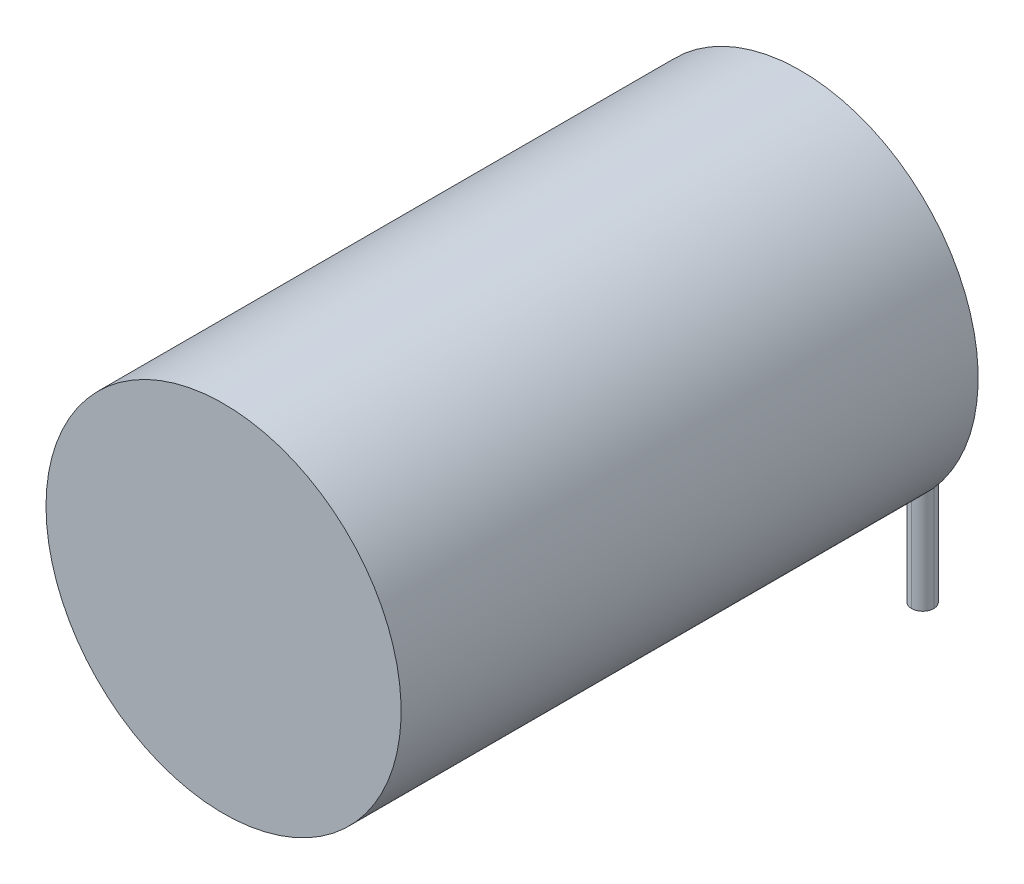
SolidWorks part; units mm, degrees
ref_plane "Front Plane" through (0, 0, 0) normal (0, 0, 1) x (1, 0, 0)
ref_plane "Top Plane" through (0, 0, 0) normal (0, 1, 0) x (1, 0, 0)
ref_plane "Right Plane" through (0, 0, 0) normal (1, 0, 0) x (0, 0, -1)
sketch "Эскиз1" plane through (0, 0, 0) normal (0, 0, 1) x (1, 0, 0)
  circle A0 centre (0, 0) radius 4
  dimension "D1" = 8
extrude "Бобышка-Вытянуть1" add sketch "Эскиз1" along normal blind 13
sketch "Эскиз2" plane through (0, 0, 0) normal (0, 0, -1) x (-1, 0, 0)
  line L0 (0, 0) -> (2, 0) construction
  line L1 (0, 0) -> (-2, 0) construction
  line L2 (2.25, 0.25) -> (2.25, -0.25)
  line L3 (-2.25, 0.25) -> (-1.75, 0.25)
  line L4 (-2.25, 0.25) -> (-2.25, -0.25)
  line L5 (-2.25, -0.25) -> (-1.75, -0.25)
  line L6 (-1.75, 0.25) -> (-1.75, -0.25)
  line L7 (-2.25, 0.25) -> (-1.75, -0.25) construction
  line L8 (-2.25, -0.25) -> (-1.75, 0.25) construction
  line L9 (1.75, 0.25) -> (1.75, -0.25)
  line L10 (1.75, -0.25) -> (2.25, 0.25) construction
  line L11 (1.75, 0.25) -> (2.25, 0.25)
  line L12 (1.75, -0.25) -> (2.25, -0.25)
  line L13 (1.75, 0.25) -> (2.25, -0.25) construction
  dimension "D1" = 0.5
  dimension "D2" = 0.5
  dimension "D3" = 0.5
  dimension "D4" = 0.5
extrude "Бобышка-Вытянуть2" add sketch "Эскиз2" along normal blind 1
sketch "Эскиз3" plane through (0, -0.25, 0) normal (0, -1, 0) x (1, 0, 0)
  line L0 (-2.25, -1) -> (-1.75, -1)
  line L1 (-1.75, -1) -> (-1.75, -0.5)
  line L2 (-1.75, -1) -> (-1.75, 0) construction
  line L3 (-1.75, -0.5) -> (-2.25, -0.5)
  line L4 (-2.25, -1) -> (-2.25, 0) construction
  line L5 (-2.25, -0.5) -> (-2.25, -1)
  line L6 (2.25, -0.5) -> (1.75, -0.5)
  line L7 (1.75, -1) -> (2.25, -1)
  line L8 (1.75, -0.5) -> (1.75, -1)
  line L9 (2.25, -1) -> (2.25, -0.5)
  line L10 (1.75, -1) -> (1.75, 0) construction
extrude "Бобышка-Вытянуть3" add sketch "Эскиз3" along normal blind 5.5
fillet "Скругление1" radius 0.25 2 edges at (-1.75, -2.75, -1) (-2.25, -2.75, -1)
fillet "Скругление2" radius 0.25 16 edges at (-1.75, 0.25, -0.375) (-1.8232, 0.25, -0.9268) (-2.25, 0.25, -0.375) (-1.75, -3, -0.5) (-2.25, -3, -0.5) (-1.75, -0.25, -0.25) (-2.25, -0.25, -0.25) (-2.1768, 0.25, -0.9268) (1.75, -0.25, -0.25) (1.75, -3, -0.5) (2.25, -3, -0.5) (2.25, -0.25, -0.25) (2.25, 0.25, -0.5) (1.75, 0.25, -0.5) (2.25, -2.75, -1) (1.75, -2.75, -1)
